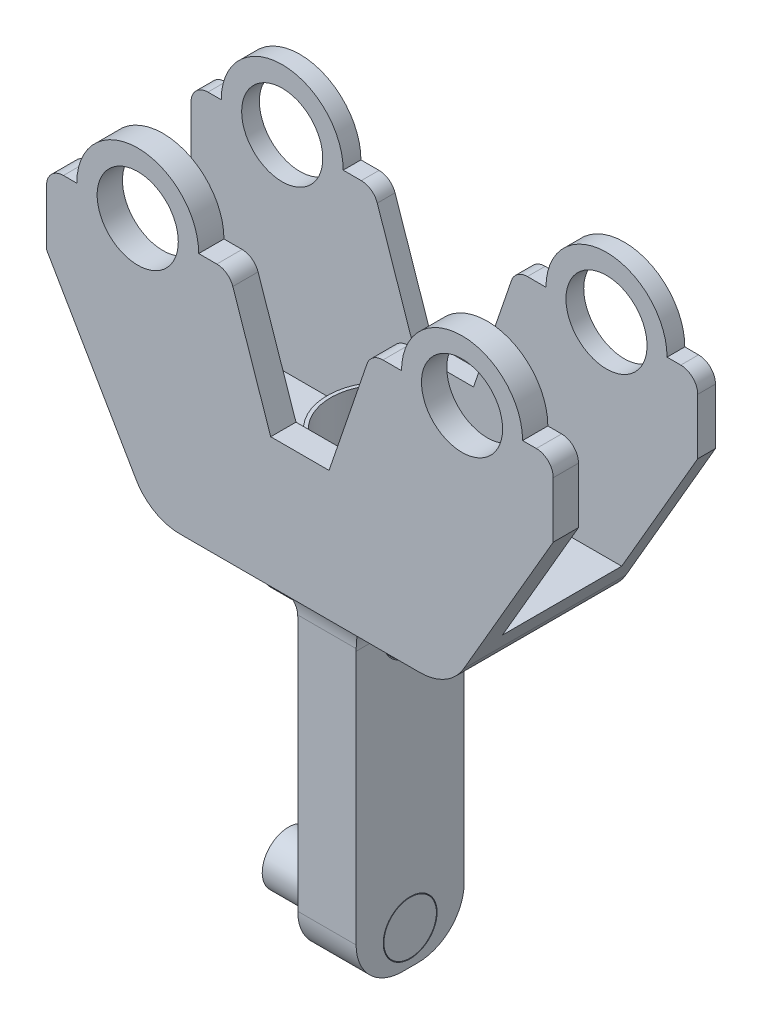
SolidWorks part; units mm, degrees
ref_plane "Plan de face" through (0, 0, 0) normal (0, 0, 1) x (1, 0, 0)
ref_plane "Plan de dessus" through (0, 0, 0) normal (0, 1, 0) x (1, 0, 0)
ref_plane "Plan de droite" through (0, 0, 0) normal (1, 0, 0) x (0, 0, -1)
sketch "Esquisse1" plane through (0, 0, 0) normal (0, 0, 1) x (1, 0, 0)
  line L0 (1.5376, 0) -> (1.5376, -4.4852) construction
  line L1 (-0.6695, 0.2562) -> (-2.2104, 2.9123)
  line L2 (0, 0.2562) -> (0, 0.577)
  line L3 (1.1061, 2.1736) -> (1.9691, 2.1736)
  line L4 (1.9691, 0.052) -> (1.9691, -4.7913)
  line L5 (1.9691, -4.7913) -> (1.1061, -4.7913)
  line L6 (-2.2104, 2.9123) -> (-2.2104, 3.9878)
  line L7 (0.4876, -4.1865) -> (2.8453, -4.1865) construction
  line L9 (1.1061, 0) -> (1.1061, -4.4852)
  line L10 (0.4876, -4.1865) -> (0.4876, -0.3052) construction
  line L11 (0.4876, -0.3052) -> (2.6528, -0.3052) construction
  line L12 (0, 0.2562) -> (3.0752, 0.2562)
  line L13 (1.1061, 0) -> (1.1061, 0.2562)
  line L14 (0, 0.2562) -> (0, 0.577)
  line L15 (1.1061, 0.2562) -> (1.9691, 0.2562)
  line L16 (0.0406, 3.9878) -> (0.4876, 3.9878)
  line L17 (1.9691, 0.052) -> (1.9691, 0.2562)
  line L18 (-2.2104, 3.9878) -> (-1.7634, 3.9878)
  line L19 (0.4876, 3.9878) -> (1.1061, 2.1736)
  line L20 (2.5876, 3.9878) -> (1.9691, 2.1736)
  line L21 (5.2855, 3.9878) -> (4.8322, 3.9878)
  line L22 (5.2855, 2.9123) -> (5.2855, 3.9878)
  line L23 (3.7447, 0.2562) -> (5.2855, 2.9123)
  line L24 (-0.6695, 0.2562) -> (3.7447, 0.2562)
  line L25 (3.041, 3.9878) -> (2.5876, 3.9878)
  line L26 (1.1061, -4.7913) -> (1.1061, -4.4852)
  line L29 (1.9691, -0.6624) -> (1.9691, -3.8879)
  arc A0 (0.0406, 3.9878) -> (-1.7634, 3.9878) centre (-0.8614, 3.9878) ccw
  arc A1 (4.8322, 3.9878) -> (3.041, 3.9878) centre (3.9366, 3.9878) ccw
extrude "Boss.-Extru.1" add sketch "Esquisse1" along normal blind 1.2 and the other way blind 1.2 contours L21 A1 L25 L20 L3 L19 L16 A0 L18 L6 L1 L24 L12 L23 L22 region at (-1.3637, 1.6285, 0)
extrude "Boss.-Extru.3" add sketch "Esquisse1<4>" along normal blind 0.8 and the other way blind 0.8 contours L26 L5 L4 L17 L12 L13 L9 region at (1.5376, -2.2676, 0)
sketch "Esquisse1<4>" plane through (0, 0, 0) normal (0, 0, 1) x (1, 0, 0) same geometry as "Esquisse1"
fillet "Congé1" radius 0.6 4 edges at (1.9691, 0.2562, 0) (1.5376, 0.2562, -0.8) (1.1061, 0.2562, 0) (1.5376, 0.2562, 0.8)
sketch "Esquisse3" plane through (1.1061, 0, 0) normal (-1, 0, 0) x (0, 0, 1)
  line L0 (0, -4.2849) -> (0, -0.4084) construction
  circle A0 centre (0, -4.2849) radius 0.3986
  circle A1 centre (0, -0.4084) radius 0.3999
extrude "Enlèv. mat.-Extru.1" cut sketch "Esquisse3" against normal blind 1.2 and the other way blind 0.8
sketch "Esquisse4" plane through (1.9691, 0, 0) normal (1, 0, 0) x (0, 0, -1)
  circle A0 centre (0, -4.2849) radius 0.3888
  circle A1 centre (0, -0.4084) radius 0.3867
extrude "Boss.-Extru.4" add sketch "Esquisse4" against normal blind 1.8 separate body
sketch "Esquisse5" plane through (0, 2.1736, 0) normal (0, 1, 0) x (1, 0, 0)
  line L1 (-2.495, 0.9372) -> (5.5456, 0.9372)
  line L2 (-2.495, 0.9372) -> (-2.495, -0.8263)
  line L3 (-2.495, -0.8263) -> (5.5456, -0.8263)
  line L4 (5.5456, 0.9372) -> (5.5456, -0.8263)
extrude "Enlèv. mat.-Extru.2" cut sketch "Esquisse5" along normal blind 2.8 and the other way blind 1.2
sketch "Esquisse6" plane through (0, 0, -1.2) normal (0, 0, -1) x (-1, 0, 0)
  circle A0 centre (-3.9366, 3.9878) radius 0.6
  circle A1 centre (0.8614, 3.9878) radius 0.6
extrude "Enlèv. mat.-Extru.3" cut sketch "Esquisse6" against normal blind 2.8
sketch "Esquisse7" plane through (0, 0.9736, 0) normal (0, 1, 0) x (1, 0, 0)
  line L0 (-1.0857, 0.0555) -> (2.2282, 0.0555) construction
  line L1 (-1.0857, 0.9372) -> (-1.0857, -0.8263) construction
  line L2 (1.5376, 0.9372) -> (1.5376, -0.3946) construction
  line L3 (1.1061, 0.9372) -> (1.9691, 0.9372) construction
  circle A0 centre (1.5376, 0.0555) radius 0.8506
  circle A1 centre (1.5376, 0.0555) radius 0.7992
extrude "Boss.-Extru.5" add sketch "Esquisse7" along normal blind 0.89
sketch "Esquisse8" plane through (0, 0.9736, 0) normal (0, 1, 0) x (1, 0, 0)
  circle A0 centre (1.5376, 0.0555) radius 0.5002
extrude "Enlèv. mat.-Extru.4" cut sketch "Esquisse8" against normal blind 0.8
fillet "Congé2" radius 0.75 2 edges at (-0.6695, 0.2562, 0) (3.7447, 0.2562, 0)
fillet "Congé3" radius 0.25 8 edges at (-2.2104, 3.9878, -1.0686) (-2.2104, 3.9878, 1.0131) (0.4876, 3.9878, 1.0131) (0.4876, 3.9878, -1.0686) (2.5876, 3.9878, -1.0686) (2.5876, 3.9878, 1.0131) (5.2855, 3.9878, 1.0131) (5.2855, 3.9878, -1.0686)
fillet "Congé4" radius 0.685 2 edges at (1.5376, -4.7913, -0.8) (1.5376, -4.7913, 0.8)
